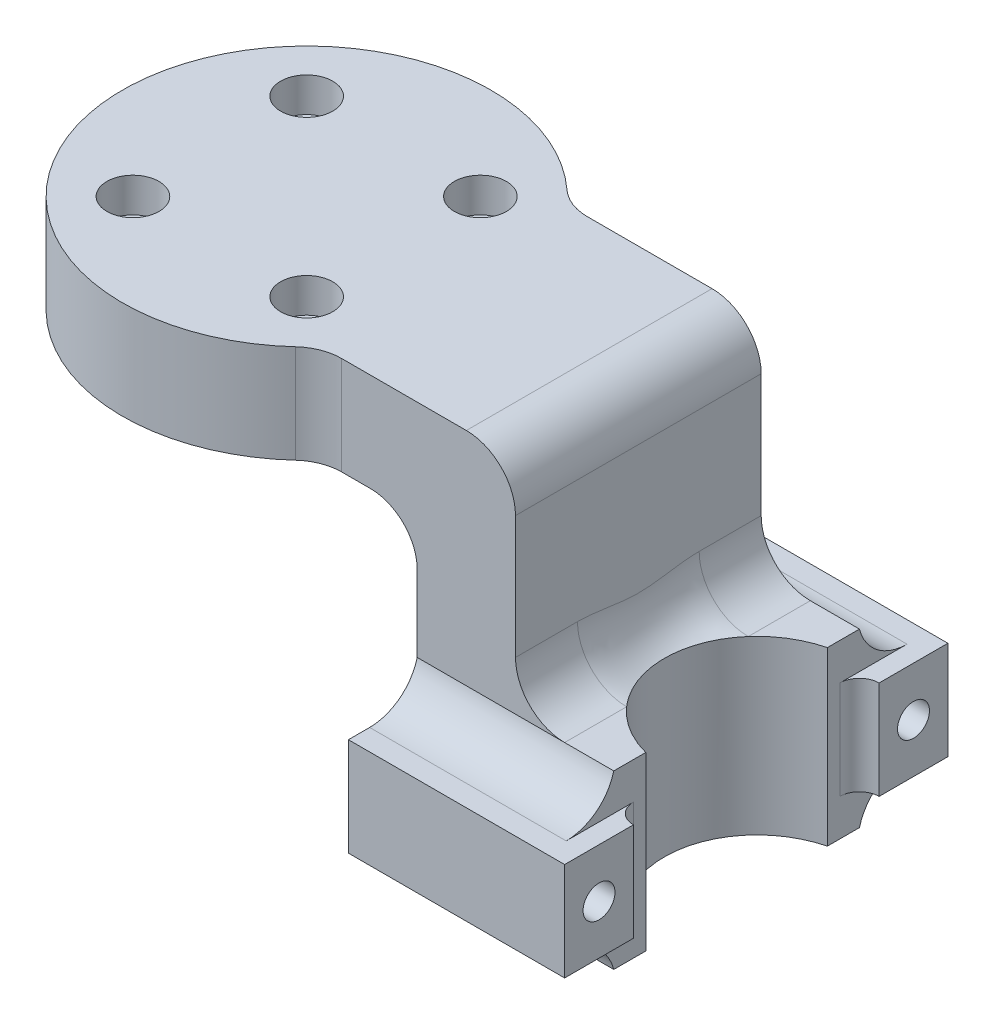
SolidWorks part; units mm, degrees
ref_plane "Front Plane" through (0, 0, 0) normal (0, 0, 1) x (1, 0, 0)
ref_plane "Top Plane" through (0, 0, 0) normal (0, 1, 0) x (1, 0, 0)
ref_plane "Right Plane" through (0, 0, 0) normal (1, 0, 0) x (0, 0, -1)
sketch "Sketch1" plane through (0, 0, 0) normal (0, 1, 0) x (1, 0, 0)
  line L1 (-25, 25) -> (25, 25)
  line L2 (-25, 25) -> (-25, -25)
  line L3 (-25, -25) -> (25, -25)
  line L4 (25, 25) -> (25, -25)
  line L5 (-25, 25) -> (25, -25) construction
  line L6 (-25, -25) -> (25, 25) construction
  ellipse E0 centre (0, 0) end of major axis (19.7, 0) minor radius 19.1
  dimension "D1" = 39.4
  dimension "D2" = 38.2
  dimension "D3" = 50
  dimension "D4" = 50
extrude "Boss-Extrude1" add sketch "Sketch1" along normal blind 35
sketch "Sketch2" plane through (0, 35, 0) normal (0, 1, 0) x (1, 0, 0)
  line L0 (25, 25) -> (-25, 25) construction
  line L1 (-5, 25) -> (25, 25)
  line L2 (-5, 25) -> (-5, -25)
  line L3 (-5, -25) -> (25, -25)
  line L4 (25, 25) -> (25, -25)
  dimension "D1" = 30
extrude "Cut-Extrude1" cut sketch "Sketch2" against normal blind 35
sketch "Sketch3" plane through (0, 35, 0) normal (0, 1, 0) x (1, 0, 0)
  line L0 (-25, -25) -> (-5, -25) construction
  line L1 (-25, 25) -> (-12, 25)
  line L2 (-25, 25) -> (-25, -25)
  line L3 (-25, -25) -> (-12, -25)
  line L4 (-12, 25) -> (-12, -25)
  dimension "D1" = 13
extrude "Boss-Extrude2" add sketch "Sketch3" along normal blind 20
sketch "Sketch4" plane through (-25, 0, 0) normal (-1, 0, 0) x (0, 0, 1)
  line L4 (18.4746, 0) -> (18.4746, 35)
  line L5 (-18.4746, 0) -> (18.4746, 0)
  line L6 (-18.4746, 35) -> (-18.4746, 0)
  line L7 (-15.1475, 35) -> (-18.4746, 35)
  line L8 (18.4746, 0) -> (18.4746, 35)
  line L9 (-18.4746, 0) -> (18.4746, 0)
  line L10 (-18.4746, 35) -> (-18.4746, 0)
  line L11 (-15.1475, 35) -> (-18.4746, 35)
  line L14 (15.1475, 35) -> (-15.1475, 35)
  line L16 (15.1475, 35) -> (-15.1475, 35)
  line L18 (18.4746, 35) -> (15.1475, 35)
  line L20 (18.4746, 35) -> (15.1475, 35)
  circle A0 centre (18.4746, 50) radius 1.5
  dimension "D3" = 3
  dimension "D1" = 0
extrude "Cut-Extrude2" cut sketch "Sketch4" against normal through all contours A0 region at (-25, 50, 18.4746)
ref_plane "Plane1" through (-12, 55, -25) normal (-1, 0, 0) x (0, 0, 1)
sketch "Sketch5" plane through (-12, 55, -25) normal (-1, 0, 0) x (0, 0, 1)
  line L1 (0, 0) -> (36.9746, 0)
  line L2 (0, 0) -> (0, -20)
  line L3 (0, -20) -> (36.9746, -20)
  line L4 (0, -55) -> (50, -55)
  line L5 (50, -55) -> (50, 0)
  line L6 (50, 0) -> (0, 0)
  line L7 (0, 0) -> (0, -55)
  line L8 (0, -55) -> (50, -55)
  line L9 (50, -55) -> (50, 0)
  line L11 (0, 0) -> (0, -55) construction
  line L12 (43.4746, -55) -> (43.4746, -20)
  line L13 (6.5254, -55) -> (43.4746, -55)
  line L14 (6.5254, -20) -> (6.5254, -55)
  line L15 (9.8525, -20) -> (6.5254, -20)
  line L16 (43.4746, -55) -> (43.4746, -20) construction
  line L17 (6.5254, -55) -> (43.4746, -55)
  line L18 (6.5254, -20) -> (6.5254, -55) construction
  line L19 (9.8525, -20) -> (6.5254, -20) construction
  line L20 (36.9746, 0) -> (36.9746, -20)
  line L24 (50, 0) -> (0, 0)
  line L27 (40.1475, -20) -> (9.8525, -20)
  line L28 (40.1475, -20) -> (9.8525, -20)
  line L29 (43.4746, -20) -> (40.1475, -20)
  line L30 (43.4746, -20) -> (40.1475, -20)
  circle A0 centre (43.4746, -5) radius 1.5 construction
  dimension "D3" = 6.5
  dimension "D1" = 0
  dimension "D2" = 0
extrude "Cut-Extrude3" cut sketch "Sketch5" along normal blind 20 contours L20 L1 L2 L3 region at (-12, 45, -6.5127)
sketch "Sketch6" plane through (-5, 0, 0) normal (1, 0, 0) x (0, 0, -1)
  line L0 (-25, 35) -> (-25, 0) construction
  line L1 (25, 0) -> (25, 35) construction
  line L2 (-39, 27.5) -> (-25, 27.5)
  line L3 (-39, 27.5) -> (-39, 7.5)
  line L4 (-39, 7.5) -> (-25, 7.5)
  line L5 (-25, 27.5) -> (-25, 7.5)
  line L6 (-39, 27.5) -> (-25, 7.5) construction
  line L7 (-39, 7.5) -> (-25, 27.5) construction
  line L8 (39, 7.5) -> (25, 7.5)
  line L9 (39, 7.5) -> (39, 27.5)
  line L10 (39, 27.5) -> (25, 27.5)
  line L11 (25, 7.5) -> (25, 27.5)
  line L12 (39, 7.5) -> (25, 27.5) construction
  line L13 (39, 27.5) -> (25, 7.5) construction
  line L14 (32, 17.5) -> (-26.1195, 17.5) construction
  circle A0 centre (32, 17.5) radius 3.25
  circle A1 centre (-32, 17.5) radius 3.25
  point P4 (-32, 17.5)
  point P9 (32, 17.5)
  point P17 (-25, 17.5)
  point P18 (-25, 17.5)
  point P19 (25, 17.5)
  point P20 (25, 17.5)
  dimension "D4" = 6.5
  dimension "D5" = 6.5
  dimension "D2" = 20
  dimension "D1" = 14
  dimension "D3" = 14
extrude "Boss-Extrude3" add sketch "Sketch6" along normal blind 4 and the other way blind 20
sketch "Sketch7" plane through (-25, 0, 0) normal (-1, 0, 0) x (0, 0, 1)
  circle A0 centre (-32, 17.5) radius 5.3
  circle A1 centre (32, 17.5) radius 5.3
  circle A2 centre (18.4746, 50) radius 3
  dimension "D1" = 10.6
  dimension "D2" = 10.6
  dimension "D3" = 6
extrude "Cut-Extrude4" cut sketch "Sketch7" against normal blind 6
sketch "Sketch8" plane through (0, 35, 0) normal (0, 1, 0) x (1, 0, 0)
  line L4 (-12, -11.9746) -> (-25, -11.9746)
  line L5 (-25, -11.9746) -> (-25, -25)
  line L6 (-25, -25) -> (-12, -25)
  line L7 (-12, -25) -> (-12, -11.9746)
  line L8 (-12, -11.9746) -> (-25, -11.9746)
  line L9 (-25, -11.9746) -> (-25, -25)
  line L10 (-25, -25) -> (-12, -25)
  line L11 (-12, -25) -> (-12, -11.9746)
  dimension "D1" = 0
extrude "Cut-Extrude5" cut sketch "Sketch8" along normal blind 30
fillet "Fillet6" radius 4 2 edges at (-5, 17.5, 25) (-5, 17.5, -25)
fillet "Fillet5" radius 10 4 edges at (-15, 7.5, 25) (-15, 27.5, 25) (-15, 27.5, -25) (-15, 7.5, -25)
sketch "Sketch9" plane through (-25, 0, 0) normal (-1, 0, 0) x (0, 0, 1)
  line L8 (39, 27.5) -> (34.6825, 27.5)
  line L9 (25, 35) -> (-25, 35)
  line L10 (-34.6825, 27.5) -> (-39, 27.5)
  line L11 (-39, 27.5) -> (-39, 7.5)
  line L12 (-39, 7.5) -> (-34.6825, 7.5)
  line L13 (-25, 0) -> (25, 0)
  line L14 (34.6825, 7.5) -> (39, 7.5)
  line L15 (39, 7.5) -> (39, 27.5)
  line L16 (39, 27.5) -> (34.6825, 27.5)
  line L17 (25, 35) -> (-25, 35)
  line L18 (-34.6825, 27.5) -> (-39, 27.5)
  line L19 (-39, 27.5) -> (-39, 7.5)
  line L20 (-39, 7.5) -> (-34.6825, 7.5)
  line L21 (-25, 0) -> (25, 0)
  line L22 (34.6825, 7.5) -> (39, 7.5)
  line L23 (39, 7.5) -> (39, 27.5)
  circle A0 centre (32, 17.5) radius 5.3 construction
  circle A1 centre (-32, 17.5) radius 5.3 construction
  circle A2 centre (32, 17.5) radius 5.3
  circle A3 centre (-32, 17.5) radius 5.3
  arc A4 (25, 35) -> (34.6825, 27.5) centre (34.6825, 37.5) ccw
  arc A5 (-34.6825, 27.5) -> (-25, 35) centre (-34.6825, 37.5) ccw
  arc A6 (-25, 0) -> (-34.6825, 7.5) centre (-34.6825, -2.5) ccw
  arc A7 (34.6825, 7.5) -> (25, 0) centre (34.6825, -2.5) ccw
  arc A8 (25, 35) -> (34.6825, 27.5) centre (34.6825, 37.5) ccw
  arc A9 (-34.6825, 27.5) -> (-25, 35) centre (-34.6825, 37.5) ccw
  arc A10 (-25, 0) -> (-34.6825, 7.5) centre (-34.6825, -2.5) ccw
  arc A11 (34.6825, 7.5) -> (25, 0) centre (34.6825, -2.5) ccw
  dimension "D1" = 0
extrude "Boss-Extrude4" add sketch "Sketch9" along normal blind 20
sketch "Sketch10" plane through (0, 35, 0) normal (0, 1, 0) x (1, 0, 0)
  line L0 (-45, -25) -> (-5, -25) construction
  line L1 (-45, 25) -> (-25, 25)
  line L2 (-45, 25) -> (-45, -25)
  line L3 (-45, -25) -> (-25, -25)
  line L4 (-25, 25) -> (-25, -25)
extrude "Boss-Extrude5" add sketch "Sketch10" along normal blind 45
fillet "Fillet7" radius 10 1 edges at (-25, 35, 0)
sketch "Sketch11" plane through (-45, 0, 0) normal (-1, 0, 0) x (0, 0, 1)
  line L0 (25, 80) -> (25, 35) construction
  line L1 (-25, 80) -> (25, 80)
  line L2 (-25, 80) -> (-25, 60)
  line L3 (-25, 60) -> (25, 60)
  line L4 (25, 80) -> (25, 60)
  dimension "D1" = 20
extrude "Boss-Extrude6" add sketch "Sketch11" along normal blind 85
fillet "Fillet8" radius 9.5 1 edges at (-45, 60, 0)
sketch "Sketch13" plane through (0, 80, 0) normal (0, 1, 0) x (1, 0, 0)
  line L0 (-55, 25) -> (-55, -25) construction
  line L1 (-25, 25) -> (-130, 25) construction
  line L2 (-130, -25) -> (-25, -25) construction
  line L3 (-130, -25) -> (-130, 25) construction
  line L4 (-55, 0) -> (-130, 0) construction
  line L5 (-120.4508, 25) -> (-130, 25)
  line L6 (-130, 25) -> (-130, -25)
  line L7 (-130, -25) -> (-120.4508, -25)
  circle A0 centre (-92.5, 0) radius 37.5
  line M2 (-25, 25) -> (-130, 25)
  line M3 (-130, 25) -> (-130, -25)
  line M4 (-130, -25) -> (-25, -25)
  dimension "D2" = 75
  dimension "D1" = 75
extrude "Boss-Extrude7" add sketch "Sketch13" against normal up to surface (20 mm away) contours A0 M2 | A0 M4 region at (-92.5, 80, -30.0791) region at (-92.5, 80, 30.0791) up to face at (-92.25, 60, 0)
extrude "Cut-Extrude6" cut sketch "Sketch13<3>" against normal blind 85 contours A0 M2 M3 | A0 L6 M4 region at (-127.2108, 80, -18.9204) region at (-127.2108, 80, 18.9204)
sketch "Sketch13<3>" plane through (0, 80, 0) normal (0, 1, 0) x (1, 0, 0) same geometry as "Sketch13"
fillet "Fillet9" radius 10 2 edges at (-64.5492, 70, -25) (-64.5492, 70, 25)
fillet "Fillet10" radius 10 1 edges at (-25, 80, 0)
sketch "Sketch14" plane through (0, 80, 0) normal (0, 1, 0) x (1, 0, 0)
  line L0 (-92.5, 25) -> (-92.5, -25) construction
  line L1 (-92.5, -25) -> (-67.5, 0) construction
  line L2 (-67.5, 0) -> (-92.5, 25) construction
  line L3 (-92.5, 25) -> (-117.5, 0) construction
  line L4 (-117.5, 0) -> (-67.5, 0) construction
  line L5 (-117.5, 0) -> (-92.5, -25) construction
  line L6 (-110.1777, -17.6777) -> (-74.8223, 17.6777) construction
  line L7 (-110.1777, 17.6777) -> (-74.8223, -17.6777) construction
  circle A0 centre (-92.5, 0) radius 25 construction
  circle A1 centre (-110.1777, 17.6777) radius 3.25
  circle A2 centre (-110.1777, -17.6777) radius 3.25
  circle A3 centre (-74.8223, -17.6777) radius 3.25
  circle A4 centre (-74.8223, 17.6777) radius 3.25
  point P10 (-92.5, 0)
  point P13 (-92.5, 0)
  dimension "D4" = 6.5
  dimension "D5" = 6.5
  dimension "D1" = 50
  dimension "D2" = 6.5
  dimension "D3" = 6.5
extrude "Cut-Extrude7" cut sketch "Sketch14" against normal blind 85
sketch "Sketch15" plane through (0, 80, 0) normal (0, 1, 0) x (1, 0, 0)
  circle A0 centre (-110.1777, 17.6777) radius 5.3
  circle A1 centre (-110.1777, -17.6777) radius 5.3
  circle A2 centre (-74.8223, -17.6777) radius 5.3
  circle A3 centre (-74.8223, 17.6777) radius 5.3
  dimension "D1" = 10.6
  dimension "D2" = 10.6
  dimension "D3" = 10.6
  dimension "D4" = 10.6
extrude "Cut-Extrude8" cut sketch "Sketch15" against normal blind 7
sketch "Sketch16" plane through (-45, 0, 0) normal (-1, 0, 0) x (0, 0, 1)
  line L1 (-25.9378, 17.5) -> (-28.9689, 22.75)
  line L2 (-28.9689, 22.75) -> (-35.0311, 22.75)
  line L3 (-35.0311, 22.75) -> (-38.0622, 17.5)
  line L4 (-38.0622, 17.5) -> (-35.0311, 12.25)
  line L5 (-35.0311, 12.25) -> (-28.9689, 12.25)
  line L6 (-28.9689, 12.25) -> (-25.9378, 17.5)
  line L7 (25.9378, 17.5) -> (28.9689, 12.25)
  line L8 (28.9689, 12.25) -> (35.0311, 12.25)
  line L9 (35.0311, 12.25) -> (38.0622, 17.5)
  line L10 (38.0622, 17.5) -> (35.0311, 22.75)
  line L11 (35.0311, 22.75) -> (28.9689, 22.75)
  line L12 (28.9689, 22.75) -> (25.9378, 17.5)
  circle A0 centre (-32, 17.5) radius 5.25 construction
  circle A1 centre (32, 17.5) radius 5.25 construction
  circle A2 centre (32, 17.5) radius 3.25 construction
  circle A3 centre (-32, 17.5) radius 3.25 construction
  circle A4 centre (32, 17.5) radius 3.25
  circle A5 centre (-32, 17.5) radius 3.25
  dimension "D1" = 10.5
  dimension "D2" = 10.5
extrude "Boss-Extrude9" add sketch "Sketch16" against normal up to surface (26 mm away) up to face at (-19, 17.5, -26.7)
extrude "Cut-Extrude11" cut sketch "Sketch16<3>" against normal blind 10
sketch "Sketch16<3>" plane through (-45, 0, 0) normal (-1, 0, 0) x (0, 0, 1) same geometry as "Sketch16"
equation "\"D3@Sketch6\"=\"D1@Sketch6\""
equation "\"D5@Sketch6\"=\"D4@Sketch6\""
equation "\"D2@Sketch7\"=\"D1@Sketch7\""
equation "\"D3@Sketch14\"=\"D2@Sketch14\""
equation "\"D4@Sketch14\"=\"D2@Sketch14\""
equation "\"D5@Sketch14\"=\"D2@Sketch14\""
equation "\"D3@Sketch15\"=\"D1@Sketch15\""
equation "\"D4@Sketch15\"=\"D1@Sketch15\""
equation "\"D2@Sketch15\"=\"D1@Sketch15\""
equation "\"D2@Sketch16\"=\"D1@Sketch16\""
